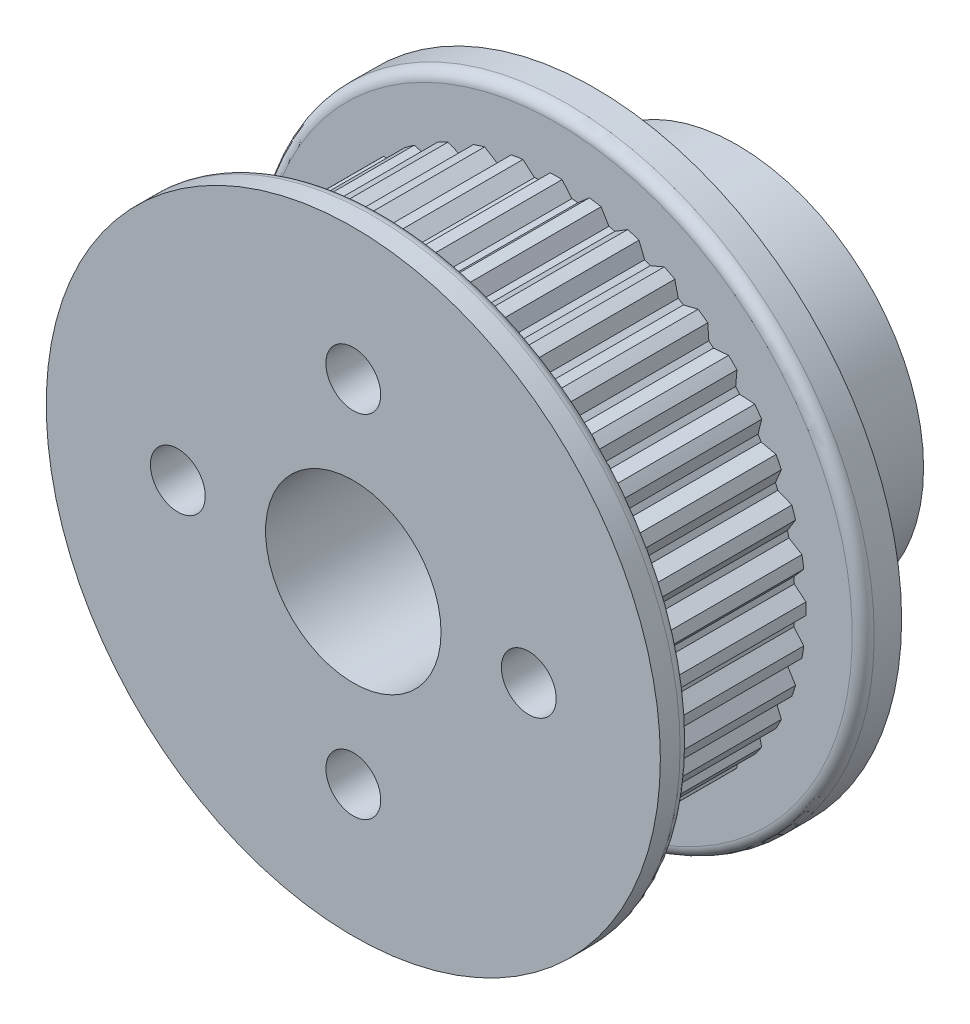
SolidWorks part; units mm, degrees
ref_plane "Front Plane" through (0, 0, 0) normal (0, 0, 1) x (1, 0, 0)
ref_plane "Top Plane" through (0, 0, 0) normal (0, 1, 0) x (1, 0, 0)
ref_plane "Right Plane" through (0, 0, 0) normal (1, 0, 0) x (0, 0, -1)
sketch "Sketch1" plane through (0, 0, 0) normal (1, 0, 0) x (0, 0, -1)
  line L0 (0, 4) -> (0, 8.5)
  line L1 (0, 8.5) -> (1.4, 8.5) construction
  line L2 (1.4, 8.5) -> (1.4, 11.39) construction
  line L3 (1.4, 11.39) -> (9.25, 11.39)
  line L4 (9.25, 14) -> (9.25, 11.39)
  line L5 (9.25, 14) -> (11, 14)
  line L6 (11, 14) -> (11, 8.5)
  line L7 (11, 8.5) -> (17.5, 8.5)
  line L8 (17.5, 8.5) -> (17.5, 4)
  line L9 (17.5, 4) -> (0, 4)
  line L10 (0, 0) -> (36.0343, 0) construction
  line L11 (0, 8.5) -> (0, 14)
  line L12 (0, 14) -> (1.4, 14)
  line L13 (1.4, 14) -> (1.4, 11.39)
  dimension "D1" = 8
  dimension "D2" = 17
  dimension "D3" = 17.5
  dimension "D4" = 28
  dimension "D5" = 22.78
  dimension "D6" = 7.85
  dimension "D7" = 1.4
  dimension "D8" = 11
revolve "Revolve1" add sketch "Sketch1" angle 360 about L10
sketch "Sketch2" plane through (0, 0, -1.4) normal (0, 0, -1) x (-1, 0, 0)
  line L0 (0, 11.39) -> (0, 0) construction
  line L1 (0, 0) -> (1.7818, 11.2498) construction
  line L2 (0.27, 11.3868) -> (0.715, 10.8565)
  line L3 (0.9921, 10.8347) -> (1.5146, 11.2888)
  line L4 (2.048, 11.2044) -> (2.4045, 10.611)
  line L5 (2.6748, 10.5461) -> (3.2619, 10.9129)
  line L6 (3.7755, 10.7461) -> (4.0348, 10.1042)
  line L7 (4.2917, 9.9978) -> (4.9289, 10.2683)
  line L8 (5.4101, 10.0231) -> (5.5658, 9.3486)
  line L9 (5.8028, 9.2033) -> (6.4746, 9.3708)
  line L10 (6.9114, 9.0534) -> (6.9597, 8.3628)
  line L11 (7.1711, 8.1823) -> (7.8608, 8.2426)
  line L12 (8.2426, 7.8608) -> (8.1823, 7.1711)
  line L13 (8.3628, 6.9597) -> (9.0534, 6.9114)
  line L14 (9.3708, 6.4746) -> (9.2033, 5.8028)
  line L15 (9.3486, 5.5658) -> (10.0231, 5.4101)
  line L16 (10.2683, 4.9289) -> (9.9978, 4.2917)
  line L17 (10.1042, 4.0348) -> (10.7461, 3.7755)
  line L18 (10.9129, 3.2619) -> (10.5461, 2.6748)
  line L19 (10.611, 2.4045) -> (11.2044, 2.048)
  line L20 (11.2888, 1.5146) -> (10.8347, 0.9921)
  line L21 (10.8565, 0.715) -> (11.3868, 0.27)
  line L22 (11.3868, -0.27) -> (10.8565, -0.715)
  line L23 (10.8347, -0.9921) -> (11.2888, -1.5146)
  line L24 (11.2044, -2.048) -> (10.611, -2.4045)
  line L25 (10.5461, -2.6748) -> (10.9129, -3.2619)
  line L26 (10.7461, -3.7755) -> (10.1042, -4.0348)
  line L27 (9.9978, -4.2917) -> (10.2683, -4.9289)
  line L28 (10.0231, -5.4101) -> (9.3486, -5.5658)
  line L29 (9.2033, -5.8028) -> (9.3708, -6.4746)
  line L30 (9.0534, -6.9114) -> (8.3628, -6.9597)
  line L31 (8.1823, -7.1711) -> (8.2426, -7.8608)
  line L32 (7.8608, -8.2426) -> (7.1711, -8.1823)
  line L33 (6.9597, -8.3628) -> (6.9114, -9.0534)
  line L34 (6.4746, -9.3708) -> (5.8028, -9.2033)
  line L35 (5.5658, -9.3486) -> (5.4101, -10.0231)
  line L36 (4.9289, -10.2683) -> (4.2917, -9.9978)
  line L37 (4.0348, -10.1042) -> (3.7755, -10.7461)
  line L38 (3.2619, -10.9129) -> (2.6748, -10.5461)
  line L39 (2.4045, -10.611) -> (2.048, -11.2044)
  line L40 (1.5146, -11.2888) -> (0.9921, -10.8347)
  line L41 (0.715, -10.8565) -> (0.27, -11.3868)
  line L42 (-0.27, -11.3868) -> (-0.715, -10.8565)
  line L43 (-0.9921, -10.8347) -> (-1.5146, -11.2888)
  line L44 (-2.048, -11.2044) -> (-2.4045, -10.611)
  line L45 (-2.6748, -10.5461) -> (-3.2619, -10.9129)
  line L46 (-3.7755, -10.7461) -> (-4.0348, -10.1042)
  line L47 (-4.2917, -9.9978) -> (-4.9289, -10.2683)
  line L48 (-5.4101, -10.0231) -> (-5.5658, -9.3486)
  line L49 (-5.8028, -9.2033) -> (-6.4746, -9.3708)
  line L50 (-6.9114, -9.0534) -> (-6.9597, -8.3628)
  line L51 (-7.1711, -8.1823) -> (-7.8608, -8.2426)
  line L52 (-8.2426, -7.8608) -> (-8.1823, -7.1711)
  line L53 (-8.3628, -6.9597) -> (-9.0534, -6.9114)
  line L54 (-9.3708, -6.4746) -> (-9.2033, -5.8028)
  line L55 (-9.3486, -5.5658) -> (-10.0231, -5.4101)
  line L56 (-10.2683, -4.9289) -> (-9.9978, -4.2917)
  line L57 (-10.1042, -4.0348) -> (-10.7461, -3.7755)
  line L58 (-10.9129, -3.2619) -> (-10.5461, -2.6748)
  line L59 (-10.611, -2.4045) -> (-11.2044, -2.048)
  line L60 (-11.2888, -1.5146) -> (-10.8347, -0.9921)
  line L61 (-10.8565, -0.715) -> (-11.3868, -0.27)
  line L62 (-11.3868, 0.27) -> (-10.8565, 0.715)
  line L63 (-10.8347, 0.9921) -> (-11.2888, 1.5146)
  line L64 (-11.2044, 2.048) -> (-10.611, 2.4045)
  line L65 (-10.5461, 2.6748) -> (-10.9129, 3.2619)
  line L66 (-10.7461, 3.7755) -> (-10.1042, 4.0348)
  line L67 (-9.9978, 4.2917) -> (-10.2683, 4.9289)
  line L68 (-10.0231, 5.4101) -> (-9.3486, 5.5658)
  line L69 (-9.2033, 5.8028) -> (-9.3708, 6.4746)
  line L70 (-9.0534, 6.9114) -> (-8.3628, 6.9597)
  line L71 (-8.1823, 7.1711) -> (-8.2426, 7.8608)
  line L72 (-7.8608, 8.2426) -> (-7.1711, 8.1823)
  line L73 (-6.9597, 8.3628) -> (-6.9114, 9.0534)
  line L74 (-6.4746, 9.3708) -> (-5.8028, 9.2033)
  line L75 (-5.5658, 9.3486) -> (-5.4101, 10.0231)
  line L76 (-4.9289, 10.2683) -> (-4.2917, 9.9978)
  line L77 (-4.0348, 10.1042) -> (-3.7755, 10.7461)
  line L78 (-3.2619, 10.9129) -> (-2.6748, 10.5461)
  line L79 (-2.4045, 10.611) -> (-2.048, 11.2044)
  line L80 (-1.5146, 11.2888) -> (-0.9921, 10.8347)
  line L81 (-0.715, 10.8565) -> (-0.27, 11.3868)
  arc A2 (0.715, 10.8565) -> (0.9921, 10.8347) centre (0, 0) cw
  arc A3 (0.27, 11.3868) -> (0, 11.39) centre (0, 0) ccw
  arc A4 (1.5146, 11.2888) -> (1.7818, 11.2498) centre (0, 0) cw
  arc A5 (2.4045, 10.611) -> (2.6748, 10.5461) centre (0, 0) cw
  arc A6 (2.048, 11.2044) -> (1.7818, 11.2498) centre (0, 0) ccw
  arc A7 (3.2619, 10.9129) -> (3.5197, 10.8325) centre (0, 0) cw
  arc A8 (4.0348, 10.1042) -> (4.2917, 9.9978) centre (0, 0) cw
  arc A9 (3.7755, 10.7461) -> (3.5197, 10.8325) centre (0, 0) ccw
  arc A10 (4.9289, 10.2683) -> (5.171, 10.1486) centre (0, 0) cw
  arc A11 (5.5658, 9.3486) -> (5.8028, 9.2033) centre (0, 0) cw
  arc A12 (5.4101, 10.0231) -> (5.171, 10.1486) centre (0, 0) ccw
  arc A13 (6.4746, 9.3708) -> (6.6949, 9.2147) centre (0, 0) cw
  arc A14 (6.9597, 8.3628) -> (7.1711, 8.1823) centre (0, 0) cw
  arc A15 (6.9114, 9.0534) -> (6.6949, 9.2147) centre (0, 0) ccw
  arc A16 (7.8608, 8.2426) -> (8.0539, 8.0539) centre (0, 0) cw
  arc A17 (8.1823, 7.1711) -> (8.3628, 6.9597) centre (0, 0) cw
  arc A18 (8.2426, 7.8608) -> (8.0539, 8.0539) centre (0, 0) ccw
  arc A19 (9.0534, 6.9114) -> (9.2147, 6.6949) centre (0, 0) cw
  arc A20 (9.2033, 5.8028) -> (9.3486, 5.5658) centre (0, 0) cw
  arc A21 (9.3708, 6.4746) -> (9.2147, 6.6949) centre (0, 0) ccw
  arc A22 (10.0231, 5.4101) -> (10.1486, 5.171) centre (0, 0) cw
  arc A23 (9.9978, 4.2917) -> (10.1042, 4.0348) centre (0, 0) cw
  arc A24 (10.2683, 4.9289) -> (10.1486, 5.171) centre (0, 0) ccw
  arc A25 (10.7461, 3.7755) -> (10.8325, 3.5197) centre (0, 0) cw
  arc A26 (10.5461, 2.6748) -> (10.611, 2.4045) centre (0, 0) cw
  arc A27 (10.9129, 3.2619) -> (10.8325, 3.5197) centre (0, 0) ccw
  arc A28 (11.2044, 2.048) -> (11.2498, 1.7818) centre (0, 0) cw
  arc A29 (10.8347, 0.9921) -> (10.8565, 0.715) centre (0, 0) cw
  arc A30 (11.2888, 1.5146) -> (11.2498, 1.7818) centre (0, 0) ccw
  arc A31 (11.3868, 0.27) -> (11.39, 0) centre (0, 0) cw
  arc A32 (10.8565, -0.715) -> (10.8347, -0.9921) centre (0, 0) cw
  arc A33 (11.3868, -0.27) -> (11.39, 0) centre (0, 0) ccw
  arc A34 (11.2888, -1.5146) -> (11.2498, -1.7818) centre (0, 0) cw
  arc A35 (10.611, -2.4045) -> (10.5461, -2.6748) centre (0, 0) cw
  arc A36 (11.2044, -2.048) -> (11.2498, -1.7818) centre (0, 0) ccw
  arc A37 (10.9129, -3.2619) -> (10.8325, -3.5197) centre (0, 0) cw
  arc A38 (10.1042, -4.0348) -> (9.9978, -4.2917) centre (0, 0) cw
  arc A39 (10.7461, -3.7755) -> (10.8325, -3.5197) centre (0, 0) ccw
  arc A40 (10.2683, -4.9289) -> (10.1486, -5.171) centre (0, 0) cw
  arc A41 (9.3486, -5.5658) -> (9.2033, -5.8028) centre (0, 0) cw
  arc A42 (10.0231, -5.4101) -> (10.1486, -5.171) centre (0, 0) ccw
  arc A43 (9.3708, -6.4746) -> (9.2147, -6.6949) centre (0, 0) cw
  arc A44 (8.3628, -6.9597) -> (8.1823, -7.1711) centre (0, 0) cw
  arc A45 (9.0534, -6.9114) -> (9.2147, -6.6949) centre (0, 0) ccw
  arc A46 (8.2426, -7.8608) -> (8.0539, -8.0539) centre (0, 0) cw
  arc A47 (7.1711, -8.1823) -> (6.9597, -8.3628) centre (0, 0) cw
  arc A48 (7.8608, -8.2426) -> (8.0539, -8.0539) centre (0, 0) ccw
  arc A49 (6.9114, -9.0534) -> (6.6949, -9.2147) centre (0, 0) cw
  arc A50 (5.8028, -9.2033) -> (5.5658, -9.3486) centre (0, 0) cw
  arc A51 (6.4746, -9.3708) -> (6.6949, -9.2147) centre (0, 0) ccw
  arc A52 (5.4101, -10.0231) -> (5.171, -10.1486) centre (0, 0) cw
  arc A53 (4.2917, -9.9978) -> (4.0348, -10.1042) centre (0, 0) cw
  arc A54 (4.9289, -10.2683) -> (5.171, -10.1486) centre (0, 0) ccw
  arc A55 (3.7755, -10.7461) -> (3.5197, -10.8325) centre (0, 0) cw
  arc A56 (2.6748, -10.5461) -> (2.4045, -10.611) centre (0, 0) cw
  arc A57 (3.2619, -10.9129) -> (3.5197, -10.8325) centre (0, 0) ccw
  arc A58 (2.048, -11.2044) -> (1.7818, -11.2498) centre (0, 0) cw
  arc A59 (0.9921, -10.8347) -> (0.715, -10.8565) centre (0, 0) cw
  arc A60 (1.5146, -11.2888) -> (1.7818, -11.2498) centre (0, 0) ccw
  arc A61 (0.27, -11.3868) -> (0, -11.39) centre (0, 0) cw
  arc A62 (-0.715, -10.8565) -> (-0.9921, -10.8347) centre (0, 0) cw
  arc A63 (-0.27, -11.3868) -> (0, -11.39) centre (0, 0) ccw
  arc A64 (-1.5146, -11.2888) -> (-1.7818, -11.2498) centre (0, 0) cw
  arc A65 (-2.4045, -10.611) -> (-2.6748, -10.5461) centre (0, 0) cw
  arc A66 (-2.048, -11.2044) -> (-1.7818, -11.2498) centre (0, 0) ccw
  arc A67 (-3.2619, -10.9129) -> (-3.5197, -10.8325) centre (0, 0) cw
  arc A68 (-4.0348, -10.1042) -> (-4.2917, -9.9978) centre (0, 0) cw
  arc A69 (-3.7755, -10.7461) -> (-3.5197, -10.8325) centre (0, 0) ccw
  arc A70 (-4.9289, -10.2683) -> (-5.171, -10.1486) centre (0, 0) cw
  arc A71 (-5.5658, -9.3486) -> (-5.8028, -9.2033) centre (0, 0) cw
  arc A72 (-5.4101, -10.0231) -> (-5.171, -10.1486) centre (0, 0) ccw
  arc A73 (-6.4746, -9.3708) -> (-6.6949, -9.2147) centre (0, 0) cw
  arc A74 (-6.9597, -8.3628) -> (-7.1711, -8.1823) centre (0, 0) cw
  arc A75 (-6.9114, -9.0534) -> (-6.6949, -9.2147) centre (0, 0) ccw
  arc A76 (-7.8608, -8.2426) -> (-8.0539, -8.0539) centre (0, 0) cw
  arc A77 (-8.1823, -7.1711) -> (-8.3628, -6.9597) centre (0, 0) cw
  arc A78 (-8.2426, -7.8608) -> (-8.0539, -8.0539) centre (0, 0) ccw
  arc A79 (-9.0534, -6.9114) -> (-9.2147, -6.6949) centre (0, 0) cw
  arc A80 (-9.2033, -5.8028) -> (-9.3486, -5.5658) centre (0, 0) cw
  arc A81 (-9.3708, -6.4746) -> (-9.2147, -6.6949) centre (0, 0) ccw
  arc A82 (-10.0231, -5.4101) -> (-10.1486, -5.171) centre (0, 0) cw
  arc A83 (-9.9978, -4.2917) -> (-10.1042, -4.0348) centre (0, 0) cw
  arc A84 (-10.2683, -4.9289) -> (-10.1486, -5.171) centre (0, 0) ccw
  arc A85 (-10.7461, -3.7755) -> (-10.8325, -3.5197) centre (0, 0) cw
  arc A86 (-10.5461, -2.6748) -> (-10.611, -2.4045) centre (0, 0) cw
  arc A87 (-10.9129, -3.2619) -> (-10.8325, -3.5197) centre (0, 0) ccw
  arc A88 (-11.2044, -2.048) -> (-11.2498, -1.7818) centre (0, 0) cw
  arc A89 (-10.8347, -0.9921) -> (-10.8565, -0.715) centre (0, 0) cw
  arc A90 (-11.2888, -1.5146) -> (-11.2498, -1.7818) centre (0, 0) ccw
  arc A91 (-11.3868, -0.27) -> (-11.39, 0) centre (0, 0) cw
  arc A92 (-10.8565, 0.715) -> (-10.8347, 0.9921) centre (0, 0) cw
  arc A93 (-11.3868, 0.27) -> (-11.39, 0) centre (0, 0) ccw
  arc A94 (-11.2888, 1.5146) -> (-11.2498, 1.7818) centre (0, 0) cw
  arc A95 (-10.611, 2.4045) -> (-10.5461, 2.6748) centre (0, 0) cw
  arc A96 (-11.2044, 2.048) -> (-11.2498, 1.7818) centre (0, 0) ccw
  arc A97 (-10.9129, 3.2619) -> (-10.8325, 3.5197) centre (0, 0) cw
  arc A98 (-10.1042, 4.0348) -> (-9.9978, 4.2917) centre (0, 0) cw
  arc A99 (-10.7461, 3.7755) -> (-10.8325, 3.5197) centre (0, 0) ccw
  arc A100 (-10.2683, 4.9289) -> (-10.1486, 5.171) centre (0, 0) cw
  arc A101 (-9.3486, 5.5658) -> (-9.2033, 5.8028) centre (0, 0) cw
  arc A102 (-10.0231, 5.4101) -> (-10.1486, 5.171) centre (0, 0) ccw
  arc A103 (-9.3708, 6.4746) -> (-9.2147, 6.6949) centre (0, 0) cw
  arc A104 (-8.3628, 6.9597) -> (-8.1823, 7.1711) centre (0, 0) cw
  arc A105 (-9.0534, 6.9114) -> (-9.2147, 6.6949) centre (0, 0) ccw
  arc A106 (-8.2426, 7.8608) -> (-8.0539, 8.0539) centre (0, 0) cw
  arc A107 (-7.1711, 8.1823) -> (-6.9597, 8.3628) centre (0, 0) cw
  arc A108 (-7.8608, 8.2426) -> (-8.0539, 8.0539) centre (0, 0) ccw
  arc A109 (-6.9114, 9.0534) -> (-6.6949, 9.2147) centre (0, 0) cw
  arc A110 (-5.8028, 9.2033) -> (-5.5658, 9.3486) centre (0, 0) cw
  arc A111 (-6.4746, 9.3708) -> (-6.6949, 9.2147) centre (0, 0) ccw
  arc A112 (-5.4101, 10.0231) -> (-5.171, 10.1486) centre (0, 0) cw
  arc A113 (-4.2917, 9.9978) -> (-4.0348, 10.1042) centre (0, 0) cw
  arc A114 (-4.9289, 10.2683) -> (-5.171, 10.1486) centre (0, 0) ccw
  arc A115 (-3.7755, 10.7461) -> (-3.5197, 10.8325) centre (0, 0) cw
  arc A116 (-2.6748, 10.5461) -> (-2.4045, 10.611) centre (0, 0) cw
  arc A117 (-3.2619, 10.9129) -> (-3.5197, 10.8325) centre (0, 0) ccw
  arc A118 (-2.048, 11.2044) -> (-1.7818, 11.2498) centre (0, 0) cw
  arc A119 (-0.9921, 10.8347) -> (-0.715, 10.8565) centre (0, 0) cw
  arc A120 (-1.5146, 11.2888) -> (-1.7818, 11.2498) centre (0, 0) ccw
  arc A121 (-0.27, 11.3868) -> (0, 11.39) centre (0, 0) cw
  circle A122 centre (0, 0) radius 11.39 construction
  circle A242 centre (0, 0) radius 15.677
  point P250 (0, 0)
  point P491 (0, 0)
  dimension "D3" = 0.51
  dimension "D1" = 40
  dimension "D2" = 40
  dimension "D4" = 0.54
extrude "Cut-Extrude1" cut sketch "Sketch2" against normal up to surface (-7.85 mm away) up to face at (11.39, 0, -9.25)
fillet "Fillet1" radius 0.5 2 edges at (14, 0, -9.25) (14, 0, -1.4)
ref_axis "Axis1" through (0, 0, -17.5) along (0, 0, 1)
sketch "Sketch3" plane through (0, 0, 0) normal (0, 0, 1) x (1, 0, 0)
  circle A4 centre (0, 8) radius 1.25
  circle A5 centre (0, 0) radius 8 construction
  circle A6 centre (8, 0) radius 1.25
  circle A7 centre (0, -8) radius 1.25
  circle A8 centre (-8, 0) radius 1.25
  point P0 (0, 0)
  point P14 (0, 0)
  dimension "D2" = 2.5
  dimension "D1" = 16
  dimension "D3" = 4
extrude "Cut-Extrude2" cut sketch "Sketch3" against normal blind 9
